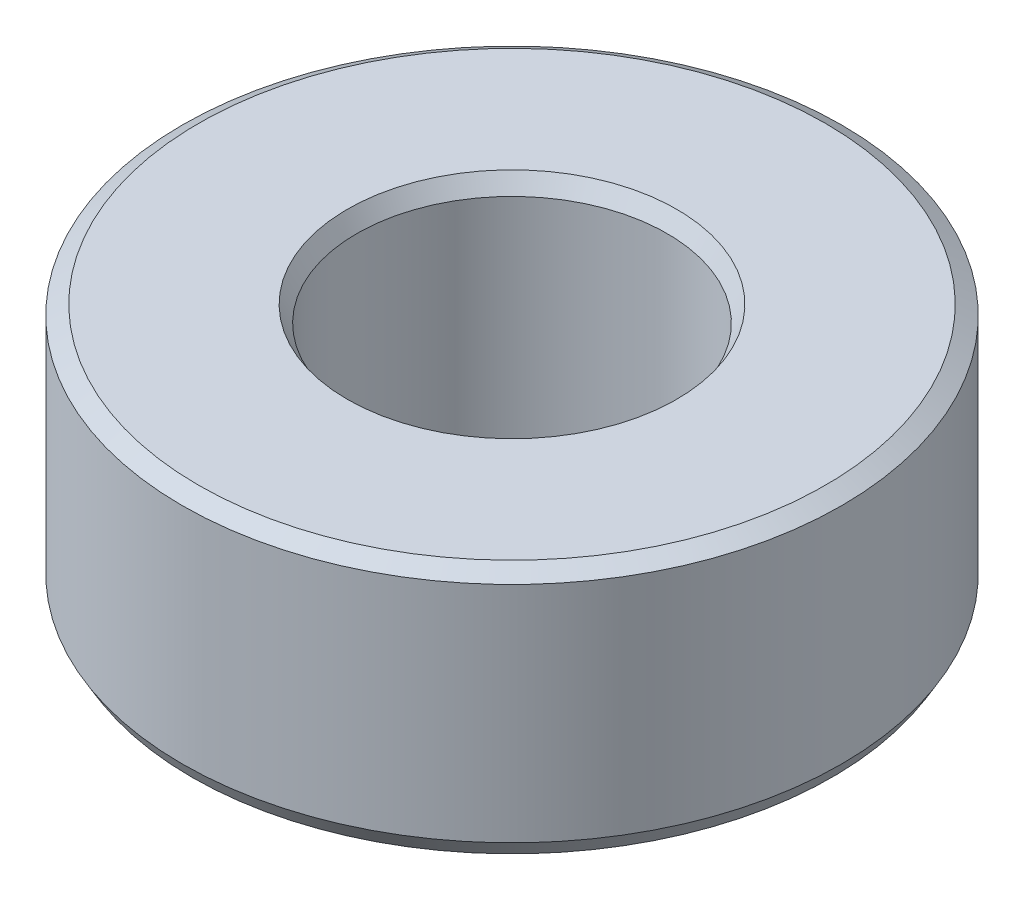
SolidWorks part; units mm, degrees
ref_plane "Front Plane" through (0, 0, 0) normal (0, 0, 1) x (1, 0, 0)
ref_plane "Top Plane" through (0, 0, 0) normal (0, 1, 0) x (1, 0, 0)
ref_plane "Right Plane" through (0, 0, 0) normal (1, 0, 0) x (0, 0, -1)
sketch "Sketch1" plane through (0, 0, 0) normal (0, 1, 0) x (1, 0, 0)
  circle A0 centre (0, 0) radius 42.5
  dimension "SLEEVE_OD" = 85
extrude "Boss-Extrude1" add sketch "Sketch1" along normal blind 32.1655
sketch "Sketch2" plane through (0, 0, 0) normal (0, 1, 0) x (1, 0, 0)
  circle A0 centre (0, 0) radius 20.0007
  dimension "BORE_D" = 40.0014
extrude "Cut-Extrude1" cut sketch "Sketch2" along normal through all
chamfer "Chamfer1" distance 1.2292 angle 59.62 4 edges at (0, 32.1655, 20.0007) (0, 0, 20.0007) (0, 0, 42.5) (0, 32.1655, 42.5) first distance on face at (0, 32.1655, 20.0007) first distance on face at (0, 0, 20.0007) first distance on face at (0, 32.1655, 42.5)
